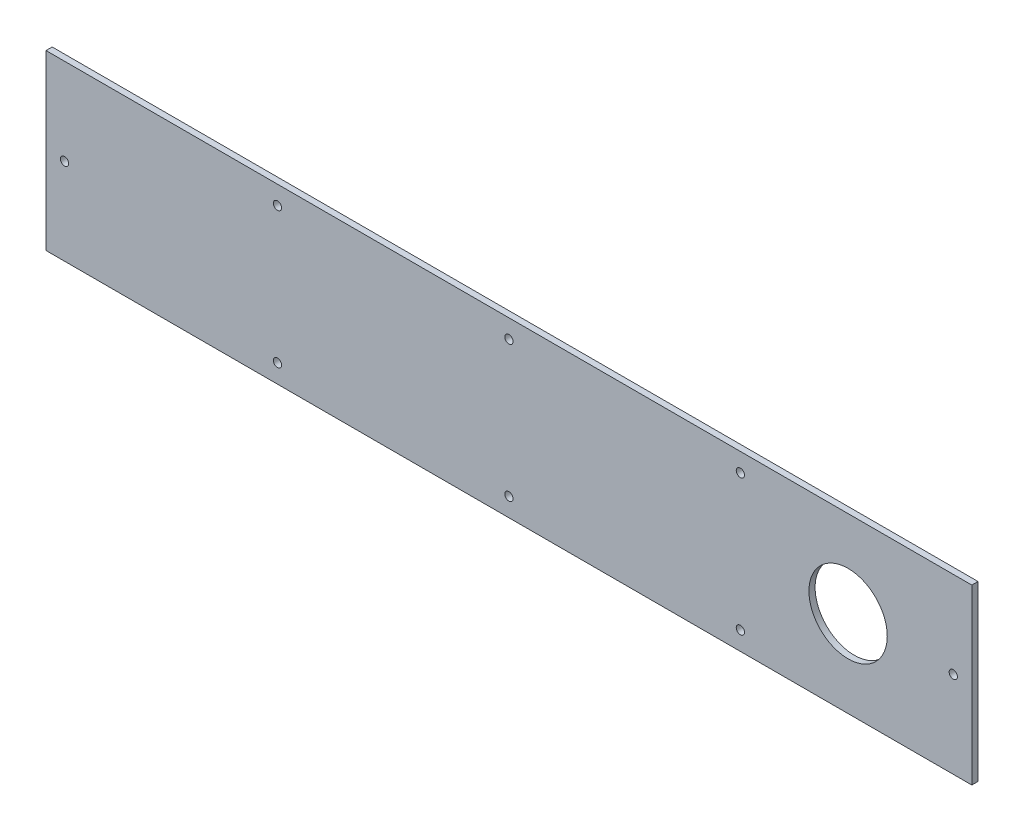
SolidWorks part; units mm, degrees
ref_plane "Piano frontale" through (0, 0, 0) normal (0, 0, 1) x (1, 0, 0)
ref_plane "Piano superiore" through (0, 0, 0) normal (0, 1, 0) x (1, 0, 0)
ref_plane "Piano destro" through (0, 0, 0) normal (1, 0, 0) x (0, 0, -1)
sketch "Schizzo1" plane through (0, 0, 0) normal (0, 0, 1) x (1, 0, 0)
  line L0 (0, 0) -> (0, 84)
  line L1 (0, 84) -> (449, 84)
  line L2 (449, 84) -> (449, 0)
  line L3 (449, 0) -> (0, 0)
  line L4 (0, 42) -> (449, 42) construction
  line L5 (224.5, 42) -> (224.5, 123.488) construction
  line L6 (0, 84) -> (224.5, 0) construction
  line L7 (224.5, 0) -> (449, 84) construction
  line L8 (336.75, 42) -> (336.75, 84) construction
  line L9 (112.25, 42) -> (112.25, 84) construction
  circle A0 centre (9, 42) radius 2
  circle A1 centre (224.5, 75) radius 2
  circle A2 centre (224.5, 9) radius 2
  circle A3 centre (440, 42) radius 2
  circle A5 centre (112.25, 75) radius 2
  circle A6 centre (336.75, 75) radius 2
  circle A7 centre (112.25, 9) radius 2
  circle A8 centre (336.75, 9) radius 2
  circle A9 centre (389, 42) radius 19
  dimension "D3" = 9
  dimension "D4" = 9
  dimension "D6" = 4
  dimension "D16" = 38
  dimension "D8" = 4
  dimension "D1" = 84
  dimension "D2" = 449
  dimension "D7" = 9
  dimension "D15" = 9
  dimension "D17" = 60
extrude "Estrusione-Estrusione1" add sketch "Schizzo1" along normal blind 3
